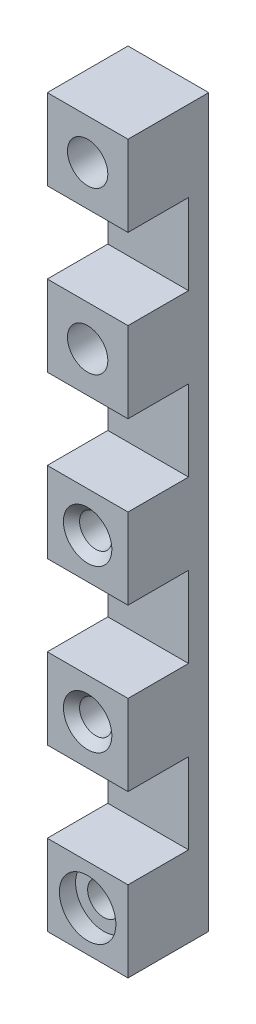
SolidWorks part; units mm, degrees
material "Сталь"
ref_plane "Спереди" through (0, 0, 0) normal (0, 0, 1) x (1, 0, 0)
ref_plane "Сверху" through (0, 0, 0) normal (0, 1, 0) x (1, 0, 0)
ref_plane "Справа" through (0, 0, 0) normal (1, 0, 0) x (0, 0, -1)
sketch "Эскиз1" plane through (0, 0, 0) normal (0, 0, 1) x (1, 0, 0)
  line L0 (-10, 0) -> (10, 0)
  line L1 (-10, -20) -> (10, -20)
  line L2 (-10, -20) -> (-10, 20)
  line L3 (-10, 20) -> (10, 20)
  line L4 (10, -20) -> (10, 20)
  line L5 (-10, -20) -> (10, 20) construction
  line L6 (-10, 20) -> (10, -20) construction
  point P0 (0, 0)
  dimension "D1" = 20
  dimension "D2" = 20
extrude "Бобышка-Вытянуть1" add sketch "Эскиз1" along normal blind 15 contours L0 L4 L3 L2 region at (0, 10, 0)
extrude "Бобышка-Вытянуть2" add sketch "Эскиз1<5>" against normal blind 5 contours L0 L4 L3 L2 | L1 L4 L0 L2 region at (0, 10, 0) region at (0, -10, 0)
sketch "Эскиз1<5>" plane through (0, 0, 0) normal (0, 0, 1) x (1, 0, 0) same geometry as "Эскиз1"
pattern_linear "Линейный массив1" count 5 spacing 40 along (0, -1, 0) of bodies 106
sketch "Эскиз2" plane through (0, 0, 0) normal (0, 0, 1) x (1, 0, 0)
  line L4 (10, -160) -> (-10, -160)
  line L5 (-10, -160) -> (-10, -180)
  line L6 (-10, -180) -> (10, -180)
  line L7 (10, -180) -> (10, -160)
  line L8 (10, -160) -> (-10, -160)
  line L9 (-10, -160) -> (-10, -180)
  line L10 (-10, -180) -> (10, -180)
  line L11 (10, -180) -> (10, -160)
  dimension "D1" = 0
extrude "Вырез-Вытянуть1" cut sketch "Эскиз2" against normal through all and the other way through all
sketch "Эскиз3" plane through (0, 0, 15) normal (0, 0, 1) x (1, 0, 0)
  line L0 (0, 20) -> (0, 0) construction
  line L1 (-10, 20) -> (10, 20) construction
  circle A0 centre (0, 10) radius 5
  dimension "D1" = 10
extrude "Вырез-Вытянуть2" cut sketch "Эскиз3" against normal through all
sketch "Эскиз4" plane through (0, 0, 15) normal (0, 0, 1) x (1, 0, 0)
  line L0 (0, -20) -> (0, -40) construction
  line L1 (-10, -20) -> (10, -20) construction
  line L2 (-10, -40) -> (10, -40) construction
  circle A0 centre (0, -30) radius 5
  dimension "D1" = 10
extrude "Вырез-Вытянуть3" cut sketch "Эскиз4" against normal blind 15
sketch "Эскиз5" plane through (0, 0, 15) normal (0, 0, 1) x (1, 0, 0)
  line L0 (0, -60) -> (0, -80) construction
  line L1 (-10, -60) -> (10, -60) construction
  line L2 (-10, -80) -> (10, -80) construction
  line L3 (0, -100) -> (0, -120) construction
  line L4 (-10, -100) -> (10, -100) construction
  line L5 (-10, -120) -> (10, -120) construction
  line L6 (0, -140) -> (0, -160) construction
  line L7 (-10, -140) -> (10, -140) construction
  line L8 (-10, -160) -> (10, -160) construction
  circle A0 centre (0, -70) radius 4
  circle A1 centre (0, -110) radius 4
  circle A2 centre (0, -150) radius 4
  dimension "D1" = 8
extrude "Вырез-Вытянуть4" cut sketch "Эскиз5" against normal through all
chamfer "Фаска1" distance 2 angle 45 1 edges at (4, -70, 15)
chamfer "Фаска2" distance 2 angle 45 1 edges at (4, -110, 15)
sketch "Эскиз6" plane through (0, 0, 15) normal (0, 0, 1) x (1, 0, 0)
  circle A0 centre (0, -150) radius 7
  dimension "D1" = 14
extrude "Вырез-Вытянуть5" cut sketch "Эскиз6" against normal blind 4
combine bodies "Соединить1" operation type add bodies to combine 112 113 114 115 117
